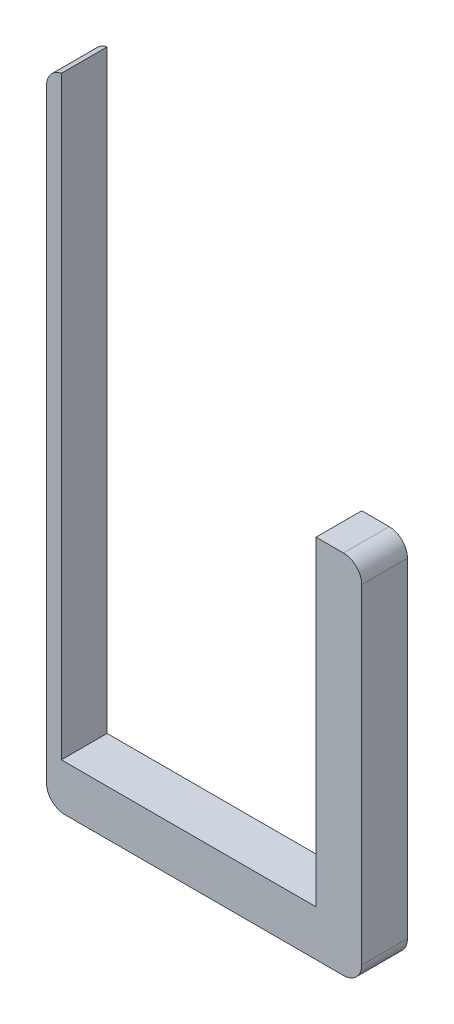
SolidWorks part; units mm, degrees
ref_plane "Front Plane" through (0, 0, 0) normal (0, 0, 1) x (1, 0, 0)
ref_plane "Top Plane" through (0, 0, 0) normal (0, 1, 0) x (1, 0, 0)
ref_plane "Right Plane" through (0, 0, 0) normal (1, 0, 0) x (0, 0, -1)
sketch "Sketch1" plane through (0, 0, 0) normal (0, 0, 1) x (1, 0, 0)
  line L0 (0, 0) -> (35.3568, 0)
  line L1 (35.3568, 0) -> (35.3568, 44.45)
  line L2 (35.3568, 44.45) -> (41.7068, 44.45)
  line L3 (41.7068, 44.45) -> (41.7068, -6.35)
  line L4 (41.7068, -6.35) -> (-2.0574, -6.35)
  line L5 (-2.0574, -6.35) -> (-2.0574, 82.55)
  line L6 (-2.0574, 82.55) -> (0, 82.55)
  line L7 (0, 82.55) -> (0, 0)
  point P3 (-1.0287, 82.55)
  dimension "D1" = 2.0574
  dimension "D2" = 35.3568
  dimension "D3" = 6.35
  dimension "D4" = 50.8
  dimension "D5" = 88.9
  dimension "D6" = 6.35
extrude "Boss-Extrude1" add sketch "Sketch1" along normal blind 6.35
fillet "Fillet1" radius 2.54 4 edges at (41.7068, 44.45, 3.175) (-2.0574, 82.55, 3.175) (-2.0574, -6.35, 3.175) (41.7068, -6.35, 3.175)
